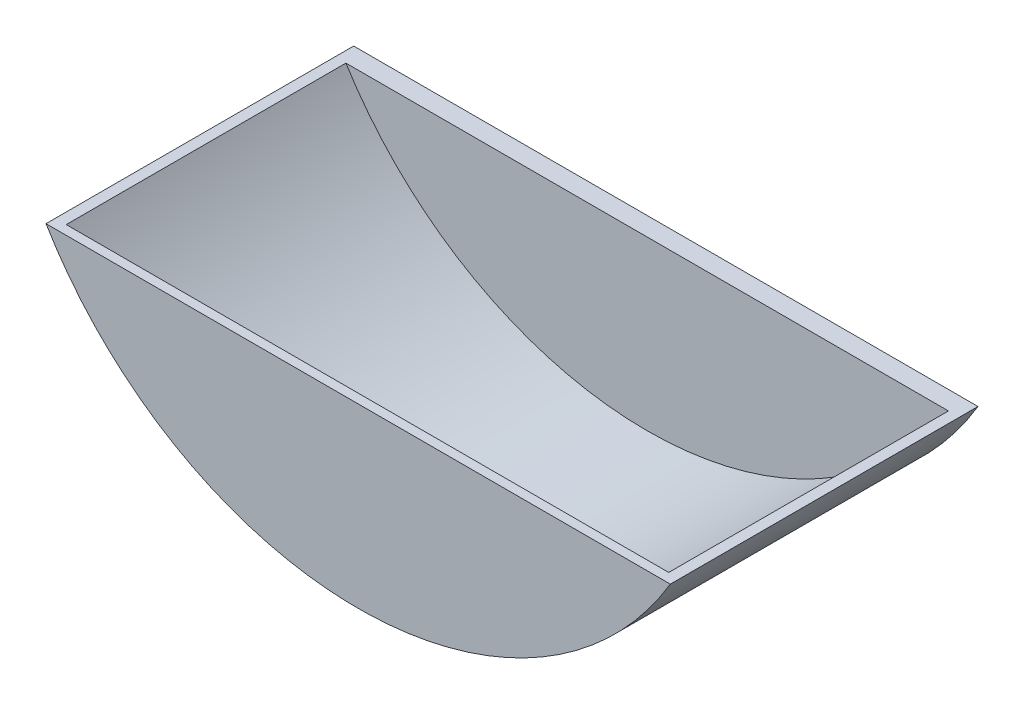
SolidWorks part; units mm, degrees
ref_plane "前视基准面" through (0, 0, 0) normal (0, 0, 1) x (1, 0, 0)
ref_plane "上视基准面" through (0, 0, 0) normal (0, 1, 0) x (1, 0, 0)
ref_plane "右视基准面" through (0, 0, 0) normal (1, 0, 0) x (0, 0, -1)
sketch "草图1" plane through (0, 0, 0) normal (0, 0, 1) x (1, 0, 0)
  line L1 (0, -100) -> (167.4067, -100)
  line L2 (167.4067, -100) -> (-167.4067, -100)
  arc A0 (-167.4067, -100) -> (167.4067, -100) centre (0, 0) ccw
  arc A2 (-161.5549, -100) -> (161.5549, -100) centre (0, 0) ccw
extrude "凸台-拉伸2" add sketch "草图1" along normal blind 150 contours L2 A0 L1 region at (164.4808, -103.4803, 0)
sketch "草图2" plane through (0, 0, 0) normal (0, 0, -1) x (-1, 0, 0)
  line L0 (-167.4067, -100) -> (167.4067, -100)
  arc A0 (-167.4067, -100) -> (167.4067, -100) centre (0, 0) ccw
extrude "凸台-拉伸3" add sketch "草图2" along normal blind 10
sketch "草图3" plane through (0, 0, 150) normal (0, 0, 1) x (1, 0, 0)
  line L0 (-167.4067, -100) -> (167.4067, -100)
  arc A0 (-167.4067, -100) -> (167.4067, -100) centre (0, 0) ccw
extrude "凸台-拉伸4" add sketch "草图3" along normal blind 5
sketch "草图4" plane through (0, 0, -10) normal (0, 0, -1) x (-1, 0, 0)
  line L0 (0, 0) -> (0, -211.2543)
  line L8 (-25, -150.2939) -> (25, -150.2939)
  line L9 (-25, -150.2939) -> (-25, -136.2939)
  line L10 (-25, -136.2939) -> (25, -136.2939)
  line L11 (25, -150.2939) -> (25, -136.2939)
  line L12 (-25, -150.2939) -> (25, -136.2939) construction
  line L13 (-25, -136.2939) -> (25, -150.2939) construction
  point P3 (0, -147.0628)
  point P8 (0, -143.2939)
extrude "切除-拉伸1" cut sketch "草图4" against normal blind 8 contours L10 L9 L8 L0 | L8 L11 L10 L0 region at (-12.5, -143.2939, -10) region at (12.5, -143.2939, -10)
fillet "圆角1" radius 15 1 edges at (0, -136.2939, -2)
fillet "圆角2" radius 3 1 edges at (0, -136.2939, -10)
fillet "圆角3" radius 1 3 edges at (0, -150.2939, -10) (-25, -142.4439, -10) (25, -142.4439, -10)
